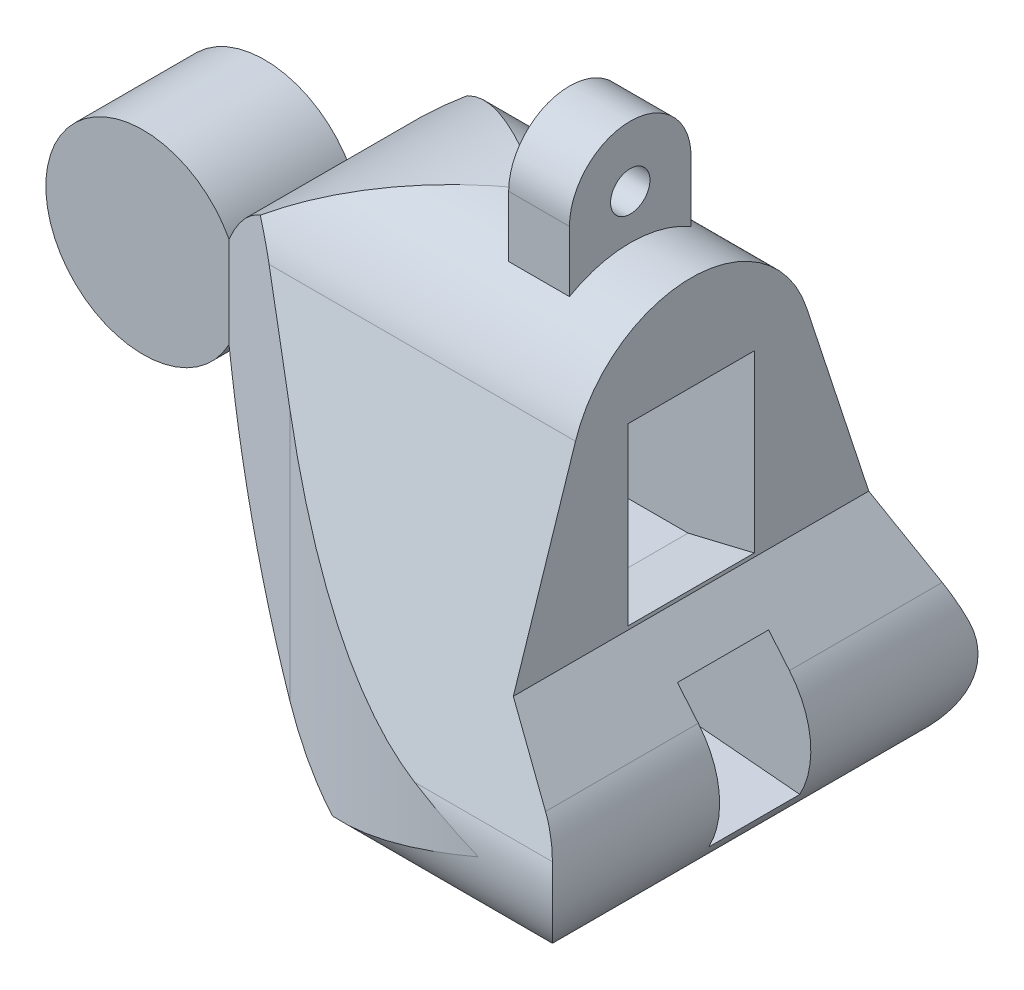
SolidWorks part; units mm, degrees
material "Polycarbonate"
ref_plane "Front Plane" through (0, 0, 0) normal (0, 0, 1) x (1, 0, 0)
ref_plane "Top Plane" through (0, 0, 0) normal (0, 1, 0) x (1, 0, 0)
ref_plane "Right Plane" through (0, 0, 0) normal (1, 0, 0) x (0, 0, -1)
sketch "Sketch2" plane through (0, 0, 0) normal (0, 0, 1) x (1, 0, 0)
  line L0 (4.4873, -2.3813) -> (4.4873, 2.3813)
  arc A0 (4.4873, 2.3813) -> (4.4873, -2.3813) centre (0, 0) ccw
  dimension "D1" = 10.16
  dimension "D2" = 4.7625
extrude "Boss-Extrude1" add sketch "Sketch2" along normal blind 6.35
sketch "Sketch3" plane through (0, 0, 0) normal (0, 0, 1) x (1, 0, 0)
  line L0 (4.4873, -2.3813) -> (4.4873, 2.3813) construction
  line L1 (4.4873, 9.525) -> (25.4423, 9.525)
  line L2 (4.4873, 9.525) -> (4.4873, -15.875)
  line L3 (4.4873, -15.875) -> (25.4423, -15.875)
  line L4 (25.4423, 9.525) -> (25.4423, -4.7625)
  line L5 (4.4873, 9.525) -> (25.4423, -15.875) construction
  line L6 (4.4873, -15.875) -> (25.4423, 9.525) construction
  line L7 (25.4423, -4.7625) -> (34.7668, -15.875)
  line L8 (34.7668, -15.875) -> (25.4423, -15.875)
  point P0 (14.9648, -3.175)
  dimension "D1" = 20.955
  dimension "D2" = 25.4
  dimension "D3" = 9.525
  dimension "D4" = 40
  dimension "D5" = 11.1125
extrude "Boss-Extrude2" add sketch "Sketch3" along normal offset from surface (22.225 mm away) 7.9375 from offset 7.9375 separate body up to face at (-0.2963, 0, 6.35) offset beyond the face yes offset against normal yes
sketch "Sketch4" plane through (0, 9.525, 0) normal (0, 1, 0) x (1, 0, 0)
  line L0 (4.4873, -6.35) -> (11.9942, -10.6841)
  line L1 (4.4873, 0) -> (11.9942, 4.3341)
  line L2 (4.4873, -14.2875) -> (4.4873, 7.9375) construction
  line L4 (25.4423, -14.2875) -> (4.4873, -14.2875) construction
  line L5 (25.4423, 7.9375) -> (4.4873, 7.9375) construction
  line L6 (4.4873, -14.2875) -> (4.4873, -6.35)
  line L7 (25.4423, 7.9375) -> (4.4873, 7.9375)
  line L8 (25.4423, -14.2875) -> (4.4873, -14.2875)
  line L9 (4.4873, 0) -> (4.4873, 7.9375)
  arc A0 (11.9942, -10.6841) -> (25.4423, -14.2875) centre (25.4423, 12.6088) ccw
  arc A1 (11.9942, 4.3341) -> (25.4423, 7.9375) centre (25.4423, -18.9588) cw
  dimension "D1" = 60
  dimension "D2" = 60
extrude "Cut-Extrude1" cut sketch "Sketch4" against normal through all
sketch "Sketch5" plane through (0, 0, 0) normal (0, 0, 1) x (1, 0, 0)
  line L0 (34.7668, -15.875) -> (25.4423, -4.7625) construction
  line L2 (11.9942, -15.875) -> (25.4423, -15.875) construction
  line L3 (22.7376, -15.875) -> (24.5536, -15.875) construction
  line L4 (25.4423, -15.875) -> (34.7668, -15.875) construction
  line L5 (34.7668, -15.875) -> (25.4423, -4.7625) construction
  line L6 (4.4873, -15.875) -> (4.4873, -2.3813)
  line L7 (25.4423, 9.525) -> (17.5048, 9.525) construction
  line L8 (25.4423, 9.525) -> (11.9942, 9.525) construction
  line L10 (4.4873, 2.3813) -> (4.4873, -2.3813) construction
  line L11 (4.4873, 2.3813) -> (4.4873, 9.525)
  line L12 (4.4873, 9.525) -> (17.5048, 9.525)
  line L13 (24.5536, -15.875) -> (34.7668, -15.875)
  line L16 (34.7668, -15.875) -> (28.2019, -8.0512)
  line L17 (4.4873, -2.3813) -> (4.8365, -3.3405)
  line L18 (4.4873, -15.875) -> (22.7376, -15.875)
  arc A1 (17.5048, 9.525) -> (4.4873, 2.3813) centre (17.5048, -5.9073) ccw
  arc A3 (4.8365, -3.3405) -> (22.7376, -15.875) centre (22.7376, 3.175) ccw
  arc A4 (24.5536, -15.875) -> (28.2019, -8.0512) centre (24.5536, -11.1125) ccw
  dimension "D1" = 20
  dimension "D2" = 7.9375
  dimension "D3" = 4.7625
  dimension "D4" = 19.05
extrude "Cut-Extrude2" cut sketch "Sketch5" along normal blind 25.24 from surface contours L18 A4 A3 L17 L6 | A4 A3 L13 L16 | A1 L12 L11 region at (8.6708, -12.2776, 0) region at (7.5722, 7.5055, 0) region at (30.4908, -13.8811, 0) starting at face at (28.5505, -12.1708, -7.9375)
sketch "Sketch7" plane through (25.4423, 0, 0) normal (1, 0, 0) x (0, 0, -1)
  line L0 (-3.175, 9.525) -> (-3.175, -7.9375) construction
  line L2 (-9.525, -15.875) -> (3.175, -15.875) construction
  line L3 (3.175, -15.875) -> (7.9375, -15.875)
  line L4 (6.7396, 9.525) -> (-13.0896, 9.525) construction
  line L5 (7.9375, -4.7625) -> (7.9375, 9.525) construction
  line L10 (7.9375, 9.525) -> (-14.2875, 9.525)
  line L11 (7.9375, -4.7625) -> (7.9375, 9.525)
  line L12 (-9.525, -15.875) -> (-14.2875, -15.875)
  line L14 (-14.0509, -9.6301) -> (-9.2096, 5.1515)
  line L15 (7.7009, -9.6301) -> (2.8596, 5.1515)
  line L18 (7.9375, -4.7625) -> (7.9375, -15.875)
  line L19 (7.9375, -15.875) -> (7.9375, -4.7625)
  line L20 (-14.2875, -15.875) -> (-14.2875, 9.525)
  arc A0 (-9.2096, 5.1515) -> (2.8596, 5.1515) centre (-3.175, 3.175) cw
  arc A3 (-14.0509, -9.6301) -> (-9.525, -15.875) centre (-9.525, -11.1125) ccw
  arc A4 (7.7009, -9.6301) -> (3.175, -15.875) centre (3.175, -11.1125) cw
  point P12 (-3.175, 9.525)
  line M3 (-14.2875, 9.525) -> (-14.2875, -4.7625)
  line M5 (7.9375, -4.7625) -> (7.9375, 9.525)
  line M6 (7.9375, 9.525) -> (-14.2875, 9.525)
  line M30 (-14.2875, -4.7625) -> (7.9375, -4.7625)
  dimension "D1" = 6.35
  dimension "D2" = 4.7625
  dimension "D3" = 25.4
  dimension "D4" = 4.7625
extrude "Cut-Extrude7" cut sketch "Sketch7" against normal blind 19.05 and the other way blind 10 contours A3 L20 L12 | L19 A4 L3 region at (25.4423, -14.8112, -6.8737) region at (25.4423, -14.8112, 13.2237)
extrude "Cut-Extrude10" cut sketch "Sketch7<4>" against normal blind 17.78 and the other way blind 10.16 contours L14 A0 L10 M3 M30 | A0 L15 M6 M30 M5 | L15 A4 L18 M30 | A3 L14 L20 M30 region at (25.4423, -6.6478, -7.3305) region at (25.4423, 4.0189, -5.3307) region at (25.4423, 4.0189, 11.6807) region at (25.4423, -6.6478, 13.6805)
sketch "Sketch7<4>" plane through (25.4423, 0, 0) normal (1, 0, 0) x (0, 0, -1) same geometry as "Sketch7"
sketch "Sketch8" plane through (0, 0, 6.35) normal (0, 0, 1) x (1, 0, 0)
  line L0 (25.4423, 4.572) -> (25.4423, -4.572)
  line L1 (25.4423, 4.572) -> (21.9842, 5.4005)
  line L2 (15.9173, 5.4005) -> (21.9842, 5.4005)
  line L3 (21.9842, -5.4005) -> (15.9173, -5.4005)
  line L4 (15.9173, 5.4005) -> (15.9173, -5.4005)
  line L5 (25.4423, -4.7625) -> (25.4423, 5.1515) construction
  line L6 (21.9842, -5.4005) -> (25.4423, -4.572)
  circle A4 centre (21.0356, 0) radius 5.08 construction
  point P12 (15.9173, 0)
  point P14 (25.4423, 0)
  dimension "D1" = 10.801
  dimension "D6" = 10.16
  dimension "D2" = 9.144
  dimension "D3" = 4.4067
  dimension "D4" = 9.525
  dimension "D5" = 3.556
extrude "Cut-Extrude8" cut sketch "Sketch8" against normal blind 6.604 from offset 0.127 contours L3 L0 L1 L2 L4 region at (20.5764, 0, 6.35)
sketch "Sketch12" plane through (25.4423, 0, 0) normal (1, 0, 0) x (0, 0, -1)
  line L1 (-6.35, 8.6743) -> (0, 8.6743)
  line L2 (-6.35, 8.6743) -> (-6.35, 11.8493)
  line L4 (0, 8.6743) -> (0, 11.8493)
  arc A0 (2.8596, 5.1515) -> (-9.2096, 5.1515) centre (-3.175, 3.175) ccw construction
  arc A1 (2.8596, 5.1515) -> (-9.2096, 5.1515) centre (-3.175, 3.175) ccw construction
  arc A2 (0, 11.8493) -> (-6.35, 11.8493) centre (-3.175, 11.8493) ccw
  point P8 (-3.175, 8.6743)
  point P9 (-3.175, 9.525)
  dimension "D1" = 6.35
  dimension "D2" = 3.175
extrude "Boss-Extrude3" add sketch "Sketch12" against normal blind 3.175 from offset 3.175 offset against normal yes
hole_wizard "#1 Clearance Hole1" positions "Sketch13" profile "Sketch14" hole size "#1" standard "ANSI Inch" end condition up to next
sketch "Sketch13" plane through (22.2673, 0, 0) normal (1, 0, 0) x (0, 0, -1)
  point P0 (-3.175, 11.8493)
sketch "Sketch14" plane through (22.2673, 11.8493, 3.175) normal (0, 1, 0) x (0, 0, -1)
  line L0 (0, 0) -> (0, 3.176)
  line L1 (0, 3.176) -> (1.0287, 3.176)
  line L2 (1.0287, 3.176) -> (1.0287, 0)
  line L5 (1.0287, 0) -> (0, 0)
  line L11 (0, -6.35) -> (0, 107.95) construction
  dimension "Thru Hole Dia." = 2.0574
  dimension "Thru Hole Depth" = 3.176
ref_plane "Plane1" through (29.3161, 0, 0) normal (1, 0, 0) x (0, 0, -1)
sketch "Sketch15" plane through (29.3161, 0, 0) normal (1, 0, 0) x (0, 0, -1)
  line L0 (-13.5338, -8.0512) -> (7.1838, -8.0512) construction
  line L1 (-5.5563, -8.0512) -> (-0.7938, -8.0512)
  line L2 (-5.5563, -8.0512) -> (-5.5563, -12.8137)
  line L3 (-5.5563, -12.8137) -> (-0.7938, -12.8137)
  line L4 (-0.7938, -8.0512) -> (-0.7938, -12.8137)
  line L5 (-5.5563, -8.0512) -> (-0.7938, -12.8137) construction
  line L6 (-5.5563, -12.8137) -> (-0.7938, -8.0512) construction
  line L7 (-13.5338, -8.0512) -> (7.1838, -8.0512) construction
  point P0 (-3.175, -10.4325)
  point P7 (0, 0)
  point P8 (0, 0)
  point P9 (0, 0)
  point P10 (-3.175, -8.0512)
  dimension "D1" = 4.7625
  dimension "D2" = 4.7625
extrude "Cut-Extrude15" cut sketch "Sketch15" against normal up to surface (7.0488 mm away) up to face at (22.2673, 11.8493, 2.1463)
sketch "Sketch16" plane through (22.2673, 0, 0) normal (1, 0, 0) x (0, 0, -1)
  line L4 (-0.7938, -12.8137) -> (-0.7938, -8.0512)
  line L5 (-0.7938, -8.0512) -> (-5.5563, -8.0512)
  line L6 (-5.5563, -8.0512) -> (-5.5563, -12.8137)
  line L7 (-5.5563, -12.8137) -> (-0.7938, -12.8137)
  line L8 (-0.7938, -12.8137) -> (-0.7938, -8.0512)
  line L9 (-0.7938, -8.0512) -> (-5.5563, -8.0512)
  line L10 (-5.5563, -8.0512) -> (-5.5563, -12.8137)
  line L11 (-5.5563, -12.8137) -> (-0.7938, -12.8137)
  dimension "D1" = 0
extrude "Cut-Extrude16" cut sketch "Sketch16" against normal through all from surface starting at face at (19.0923, 11.8493, 2.1463)
hole_wizard "#1 Clearance Hole2" positions "Sketch17" profile "Sketch18" hole size "#1" standard "ANSI Inch" end condition up to next
sketch "Sketch17" plane through (22.2673, 0, 0) normal (1, 0, 0) x (0, 0, -1)
  line L8 (-0.7938, -12.8137) -> (-0.7938, -8.0512)
  line L9 (-0.7938, -8.0512) -> (-5.5563, -8.0512)
  line L10 (-5.5563, -8.0512) -> (-5.5563, -12.8137)
  line L11 (-5.5563, -12.8137) -> (-0.7938, -12.8137)
  line L12 (-0.7938, -12.8137) -> (-0.7938, -8.0512)
  line L13 (-0.7938, -8.0512) -> (-5.5563, -8.0512)
  line L14 (-5.5563, -8.0512) -> (-5.5563, -12.8137)
  line L15 (-5.5563, -12.8137) -> (-0.7938, -12.8137)
  line L16 (-5.5563, -8.0512) -> (-0.7938, -12.8137) construction
  point P0 (-3.175, -10.4325)
  dimension "D1" = 0
sketch "Sketch18" plane through (22.2673, -10.4325, 3.175) normal (0, 1, 0) x (0, 0, -1)
  line L0 (0, 0) -> (0, 3.176)
  line L1 (0, 3.176) -> (1.0287, 3.176)
  line L2 (1.0287, 3.176) -> (1.0287, 0)
  line L5 (1.0287, 0) -> (0, 0)
  line L11 (0, -6.35) -> (0, 107.95) construction
  dimension "Thru Hole Dia." = 2.0574
  dimension "Thru Hole Depth" = 3.176
sketch "Sketch19" plane through (0, 0, 0.7938) normal (0, 0, 1) x (1, 0, 0)
  line L0 (19.0923, -12.8137) -> (14.5568, -14.029)
  line L1 (19.0923, -8.0512) -> (6.6067, -6.9589)
  line L2 (22.2673, -8.0512) -> (27.1125, -6.753)
  line L3 (12.3808, -12.8137) -> (19.0923, -12.8137)
  line L4 (19.0923, -12.8137) -> (19.0923, -8.0512)
  line L5 (19.0923, -8.0512) -> (7.3469, -8.0512)
  line L6 (12.3808, -12.8137) -> (19.0923, -12.8137) construction
  line L7 (19.0923, -12.8137) -> (19.0923, -8.0512)
  line L8 (19.0923, -8.0512) -> (7.3469, -8.0512) construction
  line L9 (28.2019, -8.0512) -> (25.4423, -4.7625) construction
  line L10 (28.2019, -8.0512) -> (27.1125, -6.753)
  line L11 (22.2673, -12.8137) -> (28.7416, -13.3801)
  line L13 (28.2019, -8.0512) -> (22.2673, -8.0512)
  line L14 (22.2673, -8.0512) -> (22.2673, -12.8137)
  line L15 (22.2673, -12.8137) -> (29.0019, -12.8137)
  line L17 (28.2019, -8.0512) -> (22.2673, -8.0512) construction
  line L18 (22.2673, -8.0512) -> (22.2673, -12.8137)
  line L19 (22.2673, -12.8137) -> (29.0019, -12.8137) construction
  arc A1 (7.3469, -8.0512) -> (12.3808, -12.8137) centre (22.7376, 3.175) ccw
  arc A6 (4.8365, -3.3405) -> (11.9942, -12.5565) centre (22.7376, 3.175) ccw construction
  arc A7 (6.6067, -6.9589) -> (14.5568, -14.029) centre (22.7376, 3.175) ccw
  arc A8 (24.5536, -15.875) -> (29.0795, -9.6301) centre (24.5536, -11.1125) ccw construction
  arc A9 (29.0019, -12.8137) -> (28.2019, -8.0512) centre (24.5536, -11.1125) ccw
  arc A12 (28.7416, -13.3801) -> (28.2019, -8.0512) centre (24.5536, -11.1125) ccw
  dimension "D2" = 15
  dimension "D3" = 5
  dimension "D5" = 15
  dimension "D6" = 5
  dimension "D1" = 0
  dimension "D4" = 0
extrude "Cut-Extrude17" cut sketch "Sketch19" along normal up to surface (4.7625 mm away) up to face at (14.4235, -10.4902, 5.5563)
